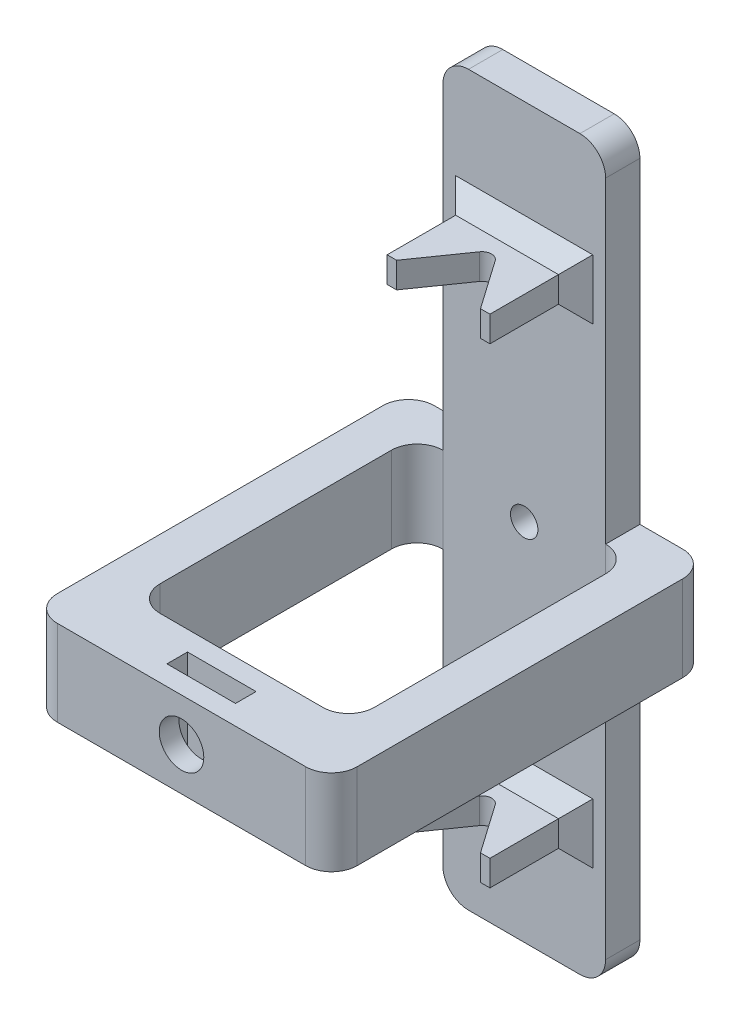
SolidWorks part; units mm, degrees
ref_plane "Front Plane" through (0, 0, 0) normal (0, 0, 1) x (1, 0, 0)
ref_plane "Top Plane" through (0, 0, 0) normal (0, 1, 0) x (1, 0, 0)
ref_plane "Right Plane" through (0, 0, 0) normal (1, 0, 0) x (0, 0, -1)
sketch "Sketch1" plane through (0, 0, 0) normal (0, 0, 1) x (1, 0, 0)
  line L1 (-7.5, 42.5) -> (7.5, 42.5)
  line L2 (-7.5, 42.5) -> (-7.5, -42.5)
  line L3 (-7.5, -42.5) -> (7.5, -42.5)
  line L4 (7.5, 42.5) -> (7.5, -42.5)
  line L5 (-7.5, 42.5) -> (7.5, -42.5) construction
  line L6 (-7.5, -42.5) -> (7.5, 42.5) construction
  point P0 (0, 0)
  dimension "D1" = 85
  dimension "D2" = 15
extrude "Boss-Extrude1" add sketch "Sketch1" along normal blind 4
sketch "Sketch2" plane through (0, 0, 4) normal (0, 0, 1) x (1, 0, 0)
  line L0 (0, 42.5) -> (0, 27.5)
  line L1 (0, -42.5) -> (0, -27.5)
  line L3 (-6, 29) -> (6, 29)
  line L4 (7.5, -42.5) -> (7.5, 42.5)
  line L5 (7.5, 42.5) -> (-7.5, 42.5)
  line L6 (-7.5, 42.5) -> (-7.5, -42.5)
  line L7 (-7.5, -42.5) -> (7.5, -42.5)
  line L9 (7.5, 42.5) -> (-7.5, 42.5)
  line L11 (-7.5, -42.5) -> (7.5, -42.5)
  line L12 (-6, 29) -> (-6, 26)
  line L13 (-6, 26) -> (6, 26)
  line L14 (6, 29) -> (6, 26)
  line L15 (-6, 29) -> (6, 26) construction
  line L16 (-6, 26) -> (6, 29) construction
  line L17 (-6, -29) -> (6, -29)
  line L18 (-6, -29) -> (-6, -26)
  line L19 (-6, -26) -> (6, -26)
  line L20 (6, -29) -> (6, -26)
  line L21 (-6, -29) -> (6, -26) construction
  line L22 (-6, -26) -> (6, -29) construction
  dimension "D2" = 15
  dimension "D3" = 15
  dimension "D4" = 3
  dimension "D5" = 12
  dimension "D6" = 3
  dimension "D7" = 12
  dimension "D1" = 0
extrude "Boss-Extrude2" add sketch "Sketch2" along normal blind 10 contours L14 L3 L12 L13 | L17 L20 L19 L18 region at (3, 28.8763, 4) region at (-3, -28.8763, 4)
sketch "Sketch3" plane through (0, 29, 0) normal (0, 1, 0) x (1, 0, 0)
  line L0 (0, -14) -> (0, -7)
  line L1 (-0.9046, -8.2934) -> (-4.896, -14)
  line L2 (0.9046, -8.2934) -> (4.896, -14)
  line L4 (6, -4) -> (-6, -4)
  line L5 (-6, -4) -> (-6, -14)
  line L6 (-6, -14) -> (6, -14)
  line L7 (6, -14) -> (6, -4)
  line L8 (6, -4) -> (-6, -4)
  line L9 (-6, -4) -> (-6, -12.896)
  line L10 (-4.896, -14) -> (4.896, -14)
  line L11 (6, -12.896) -> (6, -4)
  arc A0 (6, -12.896) -> (4.896, -14) centre (4.896, -12.896) cw
  arc A1 (-4.896, -14) -> (-6, -12.896) centre (-4.896, -12.896) cw
  arc A2 (0.9046, -8.2934) -> (-0.9046, -8.2934) centre (0, -8.9261) ccw
  line M9 (-6, -14) -> (6, -14)
  dimension "D2" = 1.104
  dimension "D4" = 1.104
  dimension "D3" = 7
  dimension "D1" = 0
extrude "Cut-Extrude1" cut sketch "Sketch3" against normal blind 60 contours L2 A2 L0 M9 | L0 A2 L1 M9 region at (-1.6555, 29, 11.7355) region at (1.6555, 29, 11.7355)
sketch "Sketch4" plane through (0, 0, 4) normal (0, 0, 1) x (1, 0, 0)
  line L0 (0, 0) -> (0, -15.4)
  circle A0 centre (0, -15.4) radius 1.6
  circle A1 centre (0, 0) radius 1.6
  dimension "D2" = 3.2
  dimension "D3" = 3.2
  dimension "D1" = 15.4
extrude "Cut-Extrude2" cut sketch "Sketch4" against normal blind 4 contours A1 | A0 region at (1.0994, -14.3006, 4) region at (-1.0994, 1.0994, 4)
sketch "Sketch5" plane through (0, 42.5, 0) normal (0, 1, 0) x (1, 0, 0)
  line L1 (7.5, 0) -> (17.5, 0)
  line L2 (7.5, 0) -> (7.5, -4)
  line L3 (7.5, -4) -> (17.5, -4)
  line L4 (17.5, 0) -> (17.5, -4)
  line L5 (-7.5, 0) -> (-17.5, 0)
  line L6 (-7.5, 0) -> (-7.5, -4)
  line L7 (-7.5, -4) -> (-17.5, -4)
  line L8 (-17.5, 0) -> (-17.5, -4)
  dimension "D1" = 10
  dimension "D2" = 10
  dimension "D3" = 4
  dimension "D4" = 4
extrude "Boss-Extrude3" add sketch "Sketch5" against normal blind 50
sketch "Sketch8" plane through (0, 0, 4) normal (0, 0, 1) x (1, 0, 0)
  line L1 (17.5, 42.5) -> (7.5, 42.5)
  line L2 (17.5, 42.5) -> (17.5, 2.5)
  line L3 (17.5, 2.5) -> (7.5, 2.5)
  line L4 (7.5, 42.5) -> (7.5, 2.5)
  line L5 (-17.5, 42.5) -> (-7.5, 42.5)
  line L6 (-17.5, 42.5) -> (-17.5, 2.5)
  line L7 (-17.5, 2.5) -> (-7.5, 2.5)
  line L8 (-7.5, 42.5) -> (-7.5, 2.5)
  dimension "D1" = 40
  dimension "D2" = 10
  dimension "D3" = 40
  dimension "D4" = 10
extrude "Cut-Extrude3" cut sketch "Sketch8" against normal blind 4
sketch "Sketch10" plane through (0, 0, 4) normal (0, 0, 1) x (1, 0, 0)
  line L1 (17.5, 2.5) -> (7.5, 2.5)
  line L2 (17.5, 2.5) -> (17.5, -7.5)
  line L3 (17.5, -7.5) -> (7.5, -7.5)
  line L4 (7.5, 2.5) -> (7.5, -7.5)
  line L5 (-17.5, 2.5) -> (-7.5, 2.5)
  line L6 (-17.5, 2.5) -> (-17.5, -7.5)
  line L7 (-17.5, -7.5) -> (-7.5, -7.5)
  line L8 (-7.5, 2.5) -> (-7.5, -7.5)
extrude "Boss-Extrude4" add sketch "Sketch10" along normal blind 40
sketch "Sketch11" plane through (7.5, 0, 0) normal (-1, 0, 0) x (0, 0, 1)
  line L1 (44, 2.5) -> (37, 2.5)
  line L2 (44, 2.5) -> (44, -7.5)
  line L3 (44, -7.5) -> (37, -7.5)
  line L4 (37, 2.5) -> (37, -7.5)
  dimension "D1" = 10
  dimension "D2" = 7
extrude "Boss-Extrude5" add sketch "Sketch11" along normal up to surface (15 mm away) up to face at (-7.5, -2.5, 24)
sketch "Sketch13" plane through (0, 2.5, 0) normal (0, 1, 0) x (1, 0, 0)
  line L3 (-7.5, -4) -> (-12.5, -4)
  line L4 (-7.5, -4) -> (-7.5, -37)
  line L5 (-7.5, -37) -> (-12.5, -37)
  line L6 (-12.5, -4) -> (-12.5, -37)
  line L7 (7.5, -4) -> (12.5, -4)
  line L8 (7.5, -4) -> (7.5, -37)
  line L9 (7.5, -37) -> (12.5, -37)
  line L10 (12.5, -4) -> (12.5, -37)
  dimension "D1" = 33
  dimension "D2" = 5
  dimension "D3" = 33
  dimension "D4" = 5
extrude "Cut-Extrude4" cut sketch "Sketch13" against normal blind 10
sketch "Sketch14" plane through (0, 0, 44) normal (0, 0, 1) x (1, 0, 0)
  line L0 (0, -7.5) -> (0, 2.5)
  line L1 (-17.5, -7.5) -> (17.5, -7.5) construction
  line L2 (17.5, 2.5) -> (-17.5, 2.5) construction
  circle A0 centre (0, -2.5) radius 2.6
  dimension "D1" = 5.2
extrude "Cut-Extrude6" cut sketch "Sketch14" against normal up to surface (7 mm away) contours L0 A0 | L0 A0 region at (-1.1035, -2.5, 44) region at (1.1035, -2.5, 44) up to face at (0, -2.5, 37)
sketch "Sketch17" plane through (7.5, 0, 0) normal (1, 0, 0) x (0, 0, -1)
  line L4 (0, -42.5) -> (0, -7.5)
  line L5 (0, -7.5) -> (-4, -7.5)
  line L6 (-4, -7.5) -> (-4, -42.5)
  line L7 (-4, -42.5) -> (0, -42.5)
  line L8 (0, -42.5) -> (0, -7.5)
  line L9 (0, -7.5) -> (-4, -7.5)
  line L10 (-4, -7.5) -> (-4, -42.5)
  line L11 (-4, -42.5) -> (0, -42.5)
  line L12 (-4, 42.5) -> (-4, 2.5)
  line L13 (-4, 2.5) -> (0, 2.5)
  line L14 (0, 2.5) -> (0, 42.5)
  line L15 (0, 42.5) -> (-4, 42.5)
  line L16 (-4, 42.5) -> (-4, 2.5)
  line L17 (-4, 2.5) -> (0, 2.5)
  line L18 (0, 2.5) -> (0, 42.5)
  line L19 (0, 42.5) -> (-4, 42.5)
  dimension "D1" = 0
  dimension "D2" = 0
extrude "Boss-Extrude6" add sketch "Sketch17" along normal blind 2
sketch "Sketch18" plane through (-7.5, 0, 0) normal (-1, 0, 0) x (0, 0, 1)
  line L4 (4, -42.5) -> (4, -7.5)
  line L5 (4, -7.5) -> (0, -7.5)
  line L6 (0, -7.5) -> (0, -42.5)
  line L7 (0, -42.5) -> (4, -42.5)
  line L8 (4, -42.5) -> (4, -7.5)
  line L9 (4, -7.5) -> (0, -7.5)
  line L10 (0, -7.5) -> (0, -42.5)
  line L11 (0, -42.5) -> (4, -42.5)
  line L12 (4, 2.5) -> (4, 42.5)
  line L13 (4, 42.5) -> (0, 42.5)
  line L14 (0, 42.5) -> (0, 2.5)
  line L15 (0, 2.5) -> (4, 2.5)
  line L16 (4, 2.5) -> (4, 42.5)
  line L17 (4, 42.5) -> (0, 42.5)
  line L18 (0, 42.5) -> (0, 2.5)
  line L19 (0, 2.5) -> (4, 2.5)
  dimension "D1" = 0
  dimension "D2" = 0
extrude "Boss-Extrude7" add sketch "Sketch18" along normal blind 2
fillet "Fillet2" radius 3 12 edges at (9.5, -42.5, 2) (-9.5, -42.5, 2) (9.5, 42.5, 2) (-9.5, 42.5, 2) (-17.5, -2.5, 0) (17.5, -2.5, 44) (-17.5, -2.5, 44) (12.5, -2.5, 37) (-12.5, -2.5, 37) (17.5, -2.5, 0) (12.5, -2.5, 4) (-12.5, -2.5, 4)
sketch "Sketch19" plane through (0, 2.5, 0) normal (0, 1, 0) x (1, 0, 0)
  line L0 (0, -44) -> (0, -37)
  line L1 (14.5, -44) -> (-14.5, -44) construction
  line L2 (-9.5, -37) -> (9.5, -37) construction
  line L4 (-4, -39.3) -> (4, -39.3)
  line L5 (-4, -39.3) -> (-4, -41.7)
  line L6 (-4, -41.7) -> (4, -41.7)
  line L7 (4, -39.3) -> (4, -41.7)
  line L8 (-4, -39.3) -> (4, -41.7) construction
  line L9 (-4, -41.7) -> (4, -39.3) construction
  point P6 (0, -40.5)
  dimension "D1" = 2.4
  dimension "D2" = 8
extrude "Cut-Extrude7" cut sketch "Sketch19" against normal blind 10 contours L5 L6 L0 L4 | L7 L4 L0 L6 region at (-2, 2.5, 40.5) region at (2, 2.5, 40.5)
chamfer "Chamfer1" distance 2 angle 45 8 edges at (-6, -27.5, 4) (0, -26, 4) (6, -27.5, 4) (0, -29, 4) (0, 29, 4) (0, 26, 4) (-6, 27.5, 4) (6, 27.5, 4)
